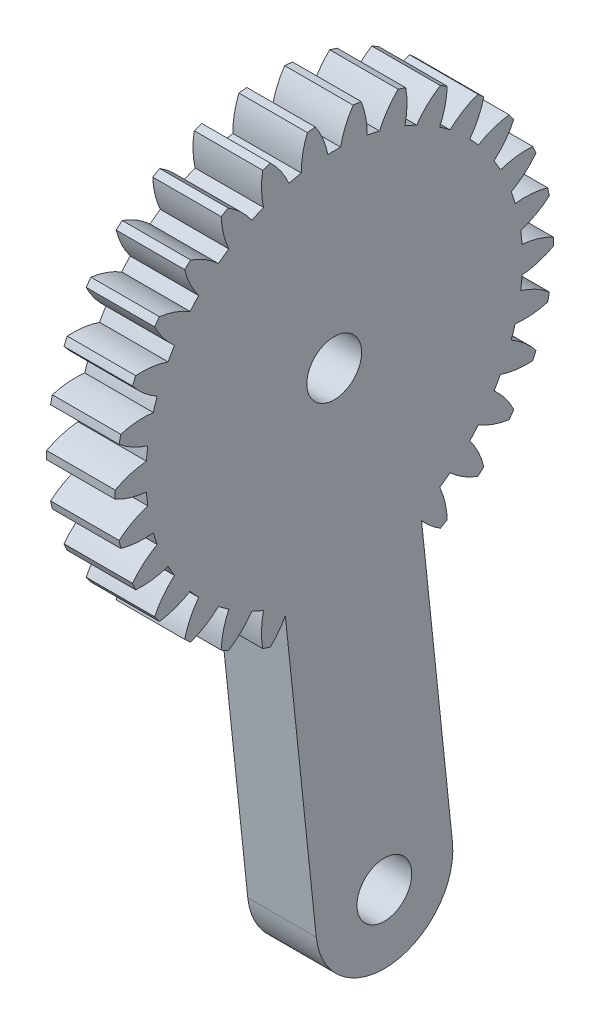
SolidWorks part; units mm, degrees
ref_plane "Plane1" through (0, 0, 0) normal (0, 0, 1) x (1, 0, 0)
ref_plane "Plane2" through (0, 0, 0) normal (0, 1, 0) x (1, 0, 0)
ref_plane "Plane3" through (0, 0, 0) normal (1, 0, 0) x (0, 0, -1)
other "Configuration Table"
sketch "HoldingSke" plane through (0, 0, 0) normal (0, 1, 0) x (1, 0, 0)
  line L0 (0, 0) -> (0.866, -0.5)
  line L1 (-15, 0) -> (100, 0) construction
  line L2 (0, 0) -> (-2.1039, 2.3779)
  line L3 (0, 0) -> (-11.863, 4.5341)
  line L4 (0, 0) -> (7.479, 4.318)
  line L5 (0, 0) -> (-46.8476, -17.4728)
  line L6 (0, 0) -> (-4.1448, -2.7965)
  line L7 (-2.1039, 2.3779) -> (8.6586, 51.2059)
  line L8 (-76.2, 54.61) -> (-76.1, 54.61)
  line L9 (-71.009, 38.7566) -> (-53.1078, 45.2721)
  line L10 (-76.2, 71.12) -> (104.1128, 71.12)
  line L11 (0, 0) -> (-5, 0)
  line L12 (-76.2, 101.6) -> (-76.162, 101.6)
  line L13 (24.9733, 27.94) -> (52.9518, 28.4284)
  line L14 (24.9733, 27.94) -> (24.9743, 27.94)
  line L15 (24.9733, 27.94) -> (100.4006, 29.5858)
  line L16 (-63.627, -1) -> (-12.827, -1)
  circle A0 centre (0, 0) radius 0.4
  circle A1 centre (0, 0) radius 13.749
  circle A2 centre (0, 0) radius 37.5
  circle A3 centre (0, 0) radius 0.4
  dimension "MHD" = 27.498
  dimension "Hub_dia" = 75
  dimension "Bore" = 0.8
  dimension "MBD" = 0.8
  dimension "Num_teeth" = 30
  dimension "Pitch" = 1
  dimension "Overall_len" = 50
  dimension "Show_teeth" = 30
  dimension "Thickness" = 5
  dimension "OAL" = 50.0001
  dimension "T_dim" = 0.1
  dimension "Ap" = 20
  dimension "H" = 19.05
  dimension "Pitch_radius" = 180.3128
  dimension "Width" = 5
  dimension "Backlash" = 0.038
  dimension "Addendum_fac" = 1
  dimension "Dedendum_fac" = 1.25
  dimension "Clearance_fac" = 0.25
  dimension "Dedendum_add" = 0.001
  dimension "Module" = 1
sketch "BasProSke" plane through (0, 0, 0) normal (0, 1, 0) x (1, 0, 0)
  line L0 (-10, 0) -> (60, 0) construction
  line L1 (0, 0) -> (0, 16)
  line L2 (0, 0) -> (5, 0)
  line L3 (5, 0) -> (5, 16)
  line L4 (5, 16) -> (0, 16)
  dimension "Thickness" = 5
  dimension "Diameter" = 32
revolve "Base-Revolve" add sketch "BasProSke" angle 360 about L0
sketch "TooCutSke" plane through (0, 0, 0) normal (1, 0, 0) x (0, 0, -1)
  line L1 (0, 0) -> (0, 107) construction
  line L2 (0, 0) -> (-0.8515, 14.9758) construction
  line L3 (0, 0) -> (-3.1323, 29.8014) construction
  line L4 (-0.8515, 14.9758) -> (-1.5661, 14.9007) construction
  arc A0 (0.4664, 13.7411) -> (-0.4664, 13.7411) centre (0, 0) ccw
  arc A1 (1.3975, 15.9644) -> (-1.3975, 15.9644) centre (0, 0) ccw
  circle A2 centre (0, 0) radius 15 construction
  circle A3 centre (0, 0) radius 14.0954 construction
  arc A4 (-0.4664, 13.7411) -> (-1.3975, 15.9644) centre (-6.3534, 12.5823) ccw
  arc A5 (1.3975, 15.9644) -> (0.4664, 13.7411) centre (6.3534, 12.5823) ccw
  dimension "Root_dia" = 27.498
  dimension "Overcut_dia" = 32.0508
  dimension "Pitch_dia" = 30
  dimension "Base_dia" = 28.1908
  dimension "Flank_rad" = 6
  dimension "Half_ang" = 6
  dimension "Half_CT" = 0.7185
extrude "ToothCut" cut sketch "TooCutSke" along normal through all
fillet "Breaks" [suppressed] radius 0.02 tangent propagation no
fillet "RootFillets" [suppressed] radius 0.251
pattern_circular "TeethCuts" count 30 every 12 about axis through (-10, 0, 0) along (1, 0, 0) of "ToothCut", "RootFillets", "Breaks"
sketch "HubNeaOneSke" plane through (0, 0, 0) normal (-1, 0, 0) x (0, 0, 1)
  circle A0 centre (0, 0) radius 13.749
  dimension "Diameter" = 27.498
extrude "HubNearOne" [suppressed] add sketch "HubNeaOneSke" along normal blind 45.0001
sketch "HubNeaBotSke" plane through (0, 0, 0) normal (-1, 0, 0) x (0, 0, 1)
  circle A0 centre (0, 0) radius 13.749
  dimension "Diameter" = 27.498
extrude "HubNearBoth" [suppressed] add sketch "HubNeaBotSke" along normal blind 22.5
ref_plane "FarPln" through (5, 0, 0) normal (1, 0, 0) x (0, 0, -1)
sketch "HubFarSke" plane through (5, 0, 0) normal (1, 0, 0) x (0, 0, -1)
  circle A0 centre (0, 0) radius 13.749
  dimension "Diameter" = 27.498
extrude "HubFar" [suppressed] add sketch "HubFarSke" along normal blind 22.5
sketch "BorSke" plane through (0, 0, 0) normal (1, 0, 0) x (0, 0, -1)
  circle A0 centre (0, 0) radius 0.4
  dimension "Diameter" = 0.8
extrude "Bore" cut sketch "BorSke" along normal mid plane 100.0001
sketch "KeySke" plane through (0, 0, 0) normal (1, 0, 0) x (0, 0, -1)
  line L0 (-0.05, 0) -> (-0.05, 0.5)
  line L1 (-0.05, 0.5) -> (0.05, 0.5)
  line L2 (0.05, 0.5) -> (0.05, 0)
  line L3 (0, 0) -> (0, 34) construction
  line L4 (-0.05, 0) -> (0.05, 0)
  dimension "Offset" = 0.5
  dimension "Width" = 0.1
extrude "Keyway" [suppressed] cut sketch "KeySke" along normal mid plane 100.0001
pattern_circular "Keyway2" [suppressed] count 2 every 90 about axis through (-10, 0, 0) along (1, 0, 0) reverse direction yes
sketch "Sketch1" plane through (5, 0, 0) normal (1, 0, 0) x (0, 0, -1)
  line L0 (0, 0) -> (3.6585, -34.8083)
  line L1 (3.6585, -34.8083) -> (4.1811, -39.7809)
  line L8 (4.9726, 0.5226) -> (9.1537, -39.2582)
  line L9 (4.9726, 0.5226) -> (-4.9726, -0.5226)
  line L10 (-4.9726, -0.5226) -> (-0.7915, -40.3035)
  line L11 (9.1537, -39.2582) -> (-0.7915, -40.3035)
  circle A1 centre (3.6585, -34.8083) radius 2
  point P19 (0, 0)
  dimension "D3" = 4
  dimension "D1" = 40
  dimension "D2" = 10
  dimension "D4" = 5
extrude "Boss-Extrude1" add sketch "Sketch1" against normal up to surface (5 mm away) contours L8 L11 L10 L9 | A1 up to face at (0, 0, -0.4)
sketch "Sketch2" plane through (5, 0, 0) normal (1, 0, 0) x (0, 0, -1)
  circle A1 centre (0, 0) radius 2
  dimension "D1" = 4
extrude "Cut-Extrude1" cut sketch "Sketch2" against normal through all
fillet "Fillet1" radius 5 2 edges at (2.5, -39.2582, -9.1537) (2.5, -40.3035, 0.7915)
equation "' \"Module@HoldingSke\" = 6.35"
equation "' \"Num_teeth@HoldingSke\" = 12"
equation "' \"Ap@HoldingSke\" =  20"
equation "' \"Ap@HoldingSke\" = 20"
equation "' \"Width@HoldingSke\" = 0.5 * 25.4"
equation "' \"Hub_dia@HoldingSke\"= 1 * 25.4"
equation "' \"Hub_dia@HoldingSke\" = 1 * 25.4"
equation "' \"Overall_len@HoldingSke\" = 1.0 * 25.4"
equation "' \"Bore@HoldingSke\" = 0.75 * 25.4"
equation "' \"T_dim@HoldingSke\" = 0.1 * 25.4"
equation "' \"Width@KeySke\" = 0.25 * 25.4"
equation "' \"Show_teeth@HoldingSke\" = 13"
equation "' \"Backlash@HoldingSke\" = 0.009 * 25.4"
equation "' \"Addendum_fac@HoldingSke\" = 1.0"
equation "' \"Dedendum_fac@HoldingSke\" = 1.25"
equation "' \"Dedendum_add@HoldingSke\" = 0.00005 * 25.4"
equation "' \"Clearance_fac@HoldingSke\" = 0.25"
equation "\"Pitch@HoldingSke\" = 1 / \"Module@HoldingSke\""
equation "\"Overcut_dia@TooCutSke\" = (\"Num_teeth@HoldingSke\" + 2 * \"Addendum_fac@HoldingSke\") / \"Pitch@HoldingSke\" + 0.002 * 25.4"
equation "\"Pitch_dia@TooCutSke\" = \"Num_teeth@HoldingSke\" / \"Pitch@HoldingSke\""
equation "\"Base_dia@TooCutSke\" = \"Num_teeth@HoldingSke\" / \"Pitch@HoldingSke\" * cos((\"Ap@HoldingSke\"  * 3.14159265 / 180))"
equation "\"Root_dia@TooCutSke\" = (\"Num_teeth@HoldingSke\" + 2) / \"Pitch@HoldingSke\" - 2 * (\"Addendum_fac@HoldingSke\" + \"Dedendum_fac@HoldingSke\") / \"Pitch@HoldingSke\" - \"Dedendum_add@HoldingSke\" * 2"
equation "\"Half_ang@TooCutSke\" = 180 / \"Num_teeth@HoldingSke\""
equation "\"Half_CT@TooCutSke\" = \"Num_teeth@HoldingSke\" / \"Pitch@HoldingSke\" * sin((3.14159265 / 2 / \"Num_teeth@HoldingSke\")) / 2 - 7 * \"Backlash@HoldingSke\" / 4"
equation "\"Flank_rad@TooCutSke\" = \"Num_teeth@HoldingSke\" / \"Pitch@HoldingSke\" / 5"
equation "\"Radius@RootFillets\" = \"Clearance_fac@HoldingSke\" / \"Pitch@HoldingSke\" + \"Dedendum_add@HoldingSke\""
equation "\"Break_rad@Breaks\" = 0.02 / \"Pitch@HoldingSke\""
equation "\"Thickness@HoldingSke\" = \"Width@HoldingSke\""
equation "\"OAL@HoldingSke\" = \"Thickness@HoldingSke\""
equation "\"MHD@HoldingSke\" = (\"Num_teeth@HoldingSke\" + 2) / \"Pitch@HoldingSke\" - 2 * (\"Addendum_fac@HoldingSke\" + \"Dedendum_fac@HoldingSke\")  / \"Pitch@HoldingSke\" - \"Dedendum_add@HoldingSke\" * 2"
equation "\"MBD@HoldingSke\" = (\"Num_teeth@HoldingSke\" + 2) / \"Pitch@HoldingSke\" - 2 * (\"Addendum_fac@HoldingSke\" + \"Dedendum_fac@HoldingSke\")  / \"Pitch@HoldingSke\" - \"Dedendum_add@HoldingSke\" * 2 - 0.002 * 25.4"
equation "\"MHD@HoldingSke\" = ((sgn( \"MHD@HoldingSke\" - \"Hub_dia@HoldingSke\" )-1)*( \"MHD@HoldingSke\" - \"Hub_dia@HoldingSke\" ))/-2+ \"Hub_dia@HoldingSke\""
equation "\"MBD@HoldingSke\" = ((sgn( \"MBD@HoldingSke\" - \"Bore@HoldingSke\" )-1)*( \"MBD@HoldingSke\" - \"Bore@HoldingSke\" ))/-2+ \"Bore@HoldingSke\""
equation "\"OAL@HoldingSke\" = ((sgn( \"OAL@HoldingSke\" - \"Overall_len@HoldingSke\" )+1)*( \"OAL@HoldingSke\" - \"Overall_len@HoldingSke\" ))/2 + \"Overall_len@HoldingSke\" + 0.000002 * 25.4"
equation "\"Num_teeth@TeethCuts\" = int( \"Show_teeth@HoldingSke\" ) + 1"
equation "\"Num_teeth@TeethCuts\" = ((sgn( \"Num_teeth@TeethCuts\" - \"Num_teeth@HoldingSke\" )-1)*( \"Num_teeth@TeethCuts\" - \"Num_teeth@HoldingSke\" ))/-2+ \"Num_teeth@HoldingSke\""
equation "\"Num_teeth@TeethCuts\" = ((sgn( \"Num_teeth@TeethCuts\" - 2.0)+1)*( \"Num_teeth@TeethCuts\" - 2.0))/2 +2.0"
equation "\"Angle@TeethCuts\" = 360.0 / \"Num_teeth@HoldingSke\""
equation "\"Diameter@BasProSke\" = (\"Num_teeth@HoldingSke\" + 2 * \"Addendum_fac@HoldingSke\") / \"Pitch@HoldingSke\""
equation "\"Thickness@BasProSke\"  = \"Thickness@HoldingSke\""
equation "' \"Fillet_rad@BasProSke\" =  \"Thickness@HoldingSke\" * 0.05"
equation "' \"Fillet_rad@BasProSke\" = \"Thickness@HoldingSke\" * 0.05"
equation "\"MHD@HoldingSke\" = ((sgn( \"MHD@HoldingSke\" - \"Root_dia@TooCutSke\" )-1)*( \"MHD@HoldingSke\" - \"Root_dia@TooCutSke\" ))/-2+ \"Root_dia@TooCutSke\""
equation "\"Diameter@HubNeaOneSke\" = \"MHD@HoldingSke\""
equation "\"Length@HubNearOne\" = \"OAL@HoldingSke\" - \"Thickness@BasProSke\""
equation "\"Diameter@HubNeaBotSke\" = \"MHD@HoldingSke\""
equation "\"Length@HubNearBoth\" = ( \"OAL@HoldingSke\" - \"Thickness@BasProSke\" ) / 2.0"
equation "\"Thickness@FarPln\" = \"Thickness@BasProSke\""
equation "\"Diameter@HubFarSke\" = \"MHD@HoldingSke\""
equation "\"Length@HubFar\" = ( \"OAL@HoldingSke\" - \"Thickness@BasProSke\" ) / 2.0"
equation "\"Diameter@BorSke\" = \"MBD@HoldingSke\""
equation "\"D1@Bore\" = \"OAL@HoldingSke\" * 2.0"
equation "\"D1@Keyway\" = \"OAL@HoldingSke\" * 2.0"
equation "\"Offset@KeySke\" = \"T_dim@HoldingSke\" + \"MBD@HoldingSke\" / 2.0"
